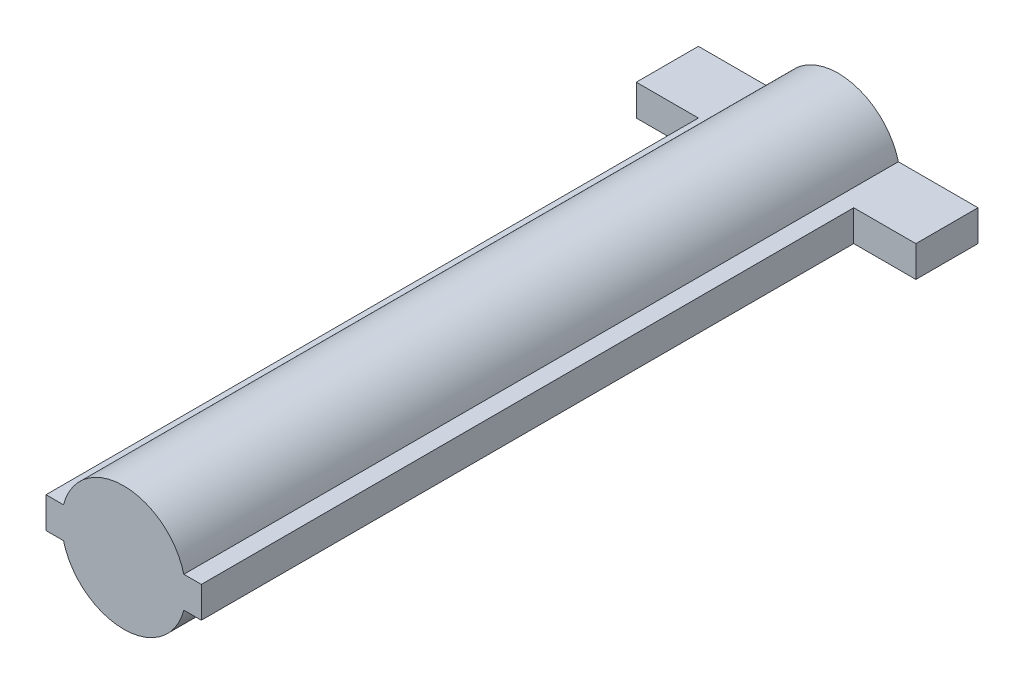
SolidWorks part; units mm, degrees
ref_plane "Front Plane" through (0, 0, 0) normal (0, 0, 1) x (1, 0, 0)
ref_plane "Top Plane" through (0, 0, 0) normal (0, 1, 0) x (1, 0, 0)
ref_plane "Right Plane" through (0, 0, 0) normal (1, 0, 0) x (0, 0, -1)
sketch "Sketch1" plane through (0, 0, 0) normal (0, 0, 1) x (1, 0, 0)
  line L0 (1.9365, 0.5) -> (4.5, 0.5)
  line L1 (-4.5, -0.5) -> (-1.9365, -0.5)
  line L2 (-4.5, -0.5) -> (-4.5, 0.5)
  line L3 (-4.5, 0.5) -> (-1.9365, 0.5)
  line L4 (4.5, -0.5) -> (4.5, 0.5)
  line L5 (-4.5, -0.5) -> (4.5, 0.5) construction
  line L6 (-4.5, 0.5) -> (4.5, -0.5) construction
  line L7 (1.9365, -0.5) -> (4.5, -0.5)
  arc A0 (-1.9365, -0.5) -> (1.9365, -0.5) centre (0, 0) ccw
  arc A1 (1.9365, 0.5) -> (-1.9365, 0.5) centre (0, 0) ccw
  dimension "D1" = 4
  dimension "D2" = 9
  dimension "D3" = 1
extrude "Boss-Extrude2" add sketch "Sketch1" along normal blind 2
sketch "Sketch2" plane through (0, 0, 2) normal (0, 0, 1) x (1, 0, 0)
  line L0 (1.9365, 0.5) -> (2.5, 0.5)
  line L1 (-2.5, -0.5) -> (-1.9365, -0.5)
  line L2 (-2.5, -0.5) -> (-2.5, 0.5)
  line L3 (-2.5, 0.5) -> (-1.9365, 0.5)
  line L4 (2.5, -0.5) -> (2.5, 0.5)
  line L5 (-2.5, -0.5) -> (2.5, 0.5) construction
  line L6 (-2.5, 0.5) -> (2.5, -0.5) construction
  line L7 (1.9365, -0.5) -> (2.5, -0.5)
  arc A0 (-1.9365, -0.5) -> (1.9365, -0.5) centre (0, 0) ccw
  arc A1 (1.9365, 0.5) -> (-1.9365, 0.5) centre (0, 0) ccw
  dimension "D1" = 4
  dimension "D2" = 5
  dimension "D3" = 1
extrude "Boss-Extrude4" add sketch "Sketch2<2>" along normal blind 21
sketch "Sketch2<2>" plane through (0, 0, 2) normal (0, 0, 1) x (1, 0, 0) same geometry as "Sketch2"
extrude "Boss-Extrude3" add sketch "Sketch2" along normal blind 20
